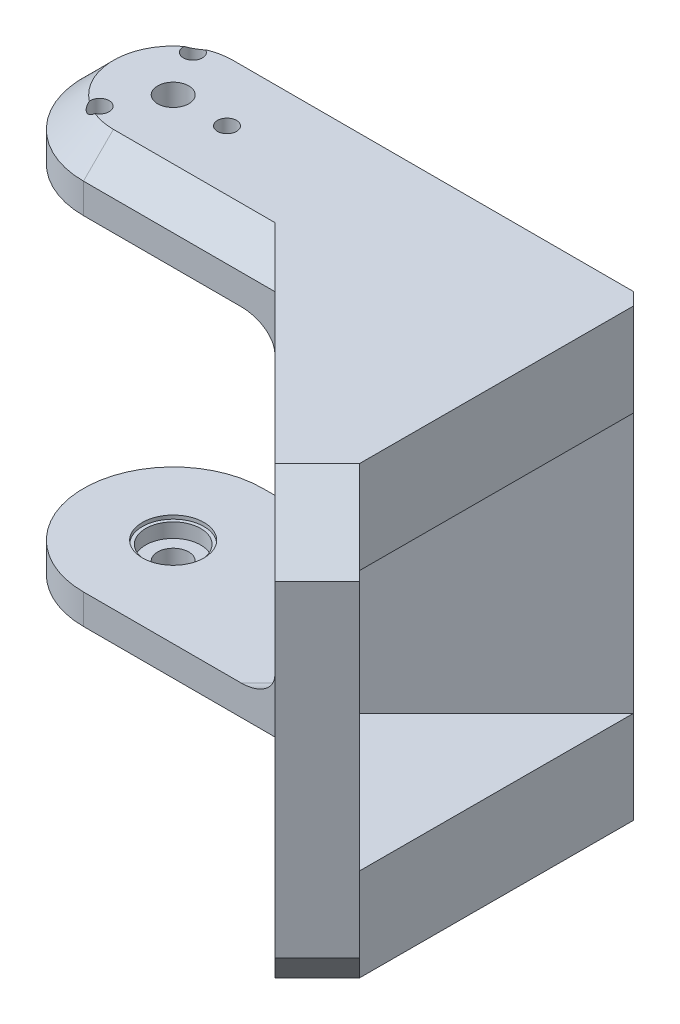
SolidWorks part; units mm, degrees
ref_plane "前视基准面" through (0, 0, 0) normal (0, 0, 1) x (1, 0, 0)
ref_plane "上视基准面" through (0, 0, 0) normal (0, 1, 0) x (1, 0, 0)
ref_plane "右视基准面" through (0, 0, 0) normal (1, 0, 0) x (0, 0, -1)
other "Configuration Table"
sketch "草图1" plane through (0, 0, 0) normal (0, 1, 0) x (1, 0, 0)
  line L0 (0, 0) -> (9, 0) construction
  line L1 (0, 15) -> (62, 15)
  line L3 (32, -15) -> (0, -15)
  line L4 (62, 15) -> (32, -15)
  arc A0 (0, 15) -> (0, -15) centre (0, 0) ccw
  circle A1 centre (9, 0) radius 1.6
  circle A2 centre (-4.5, -7.7942) radius 1.6
  circle A3 centre (-4.5, 7.7942) radius 1.6
  dimension "D1" = 30
  dimension "D2" = 32
  dimension "D3" = 3.2
  dimension "D5" = 9
  dimension "D6" = 45
  dimension "D4" = 3
extrude "凸台-拉伸1" add sketch "草图1" along normal blind 10
sketch "草图3" plane through (23.5, 0, 23.5) normal (0.7071, 0, 0.7071) x (0.7071, 0, -0.7071)
  line L0 (54.4472, 10) -> (54.4472, 0) construction
  line L1 (12.0208, 10) -> (54.4472, 10)
  line L2 (12.0208, 10) -> (12.0208, -64.5)
  line L3 (12.0208, -64.5) -> (54.4472, -64.5)
  line L4 (54.4472, 10) -> (54.4472, -64.5)
  dimension "D1" = 74.5
extrude "凸台-拉伸2" add sketch "草图3" along normal blind 10
sketch "草图6" plane through (0, 10, 0) normal (0, 1, 0) x (1, 0, 0)
  line L0 (39.0711, -22.0711) -> (68.9817, -51.9817)
  line L1 (68.9817, -51.9817) -> (76.0528, -44.9106)
  line L2 (76.0528, -44.9106) -> (46.1421, -15)
  line L3 (69.0711, 7.9289) -> (39.0711, -22.0711) construction
  line L4 (46.1421, -15) -> (39.0711, -22.0711)
  dimension "D1" = 10
  dimension "D2" = 42.3
extrude "凸台-拉伸3" add sketch "草图6" against normal up to surface (74.5 mm away) up to face at (50.5355, -64.5, 3.5355)
sketch "草图7" plane through (15.5711, 0, -15.5711) normal (0.7071, 0, -0.7071) x (-0.7071, 0, -0.7071)
  line L0 (-79.884, -11.75) -> (-48.884, -11.75) construction
  line L1 (-79.884, -11.75) -> (-79.884, -42.75) construction
  line L4 (-85.534, -64.5) -> (-85.534, 10) construction
  line L5 (-85.534, -27.25) -> (-43.234, -27.25) construction
  line L6 (-43.234, -64.5) -> (-43.234, 10) construction
  circle A0 centre (-79.884, -11.75) radius 1.6
  circle A1 centre (-48.884, -11.75) radius 1.6
  circle A2 centre (-48.884, -42.75) radius 1.6
  circle A3 centre (-79.884, -42.75) radius 1.6
  dimension "D6" = 3.2
  dimension "D7" = 15.5
  dimension "D8" = 5.65
  dimension "D3" = 90
  dimension "D4" = 31
  dimension "D5" = 31
  dimension "D1" = 2
  dimension "D2" = 2
extrude "切除-拉伸1" cut sketch "草图7" against normal up to surface (10 mm away) up to face at (46.7927, -21.8, 29.7927)
sketch "草图9" plane through (15.5711, 0, -15.5711) normal (0.7071, 0, -0.7071) x (-0.7071, 0, -0.7071)
  line L0 (-79.884, -11.75) -> (-48.884, -42.75) construction
  circle A0 centre (-64.384, -27.25) radius 18.6
  dimension "D1" = 37.2
extrude "切除-拉伸2" cut sketch "草图9" against normal blind 7
sketch "草图10" plane through (10.6213, 0, -10.6213) normal (0.7071, 0, -0.7071) x (-0.7071, 0, -0.7071)
  circle A0 centre (-64.384, -27.25) radius 13
  circle A1 centre (-64.384, -27.25) radius 18.6 construction
  dimension "D1" = 26
extrude "切除-拉伸3" cut sketch "草图10" against normal blind 7
chamfer "倒角1" distance 10 angle 45 2 edges at (72.5172, -64.5, 48.4462) (72.5172, 10, 48.4462)
sketch "草图11" plane through (0, 10, 0) normal (0, 1, 0) x (1, 0, 0)
  line L0 (69.0711, 7.9289) -> (68.9817, -37.8395)
  line L1 (68.9817, -37.8395) -> (46.1421, -15)
  line L2 (46.1421, -15) -> (69.0711, 7.9289)
extrude "凸台-拉伸4" add sketch "草图11" against normal blind 15.5
sketch "草图12" plane through (0, -64.5, 0) normal (0, -1, 0) x (1, 0, 0)
  line L3 (46.1421, 15) -> (69.0711, -7.9289)
  line L4 (69.0711, -7.9289) -> (68.9817, 37.8395)
  line L5 (68.9817, 37.8395) -> (46.1421, 15)
  line L6 (46.1421, 15) -> (69.0711, -7.9289)
  line L7 (69.0711, -7.9289) -> (68.9817, 37.8395)
  line L8 (68.9817, 37.8395) -> (46.1421, 15)
  dimension "D1" = 0
extrude "凸台-拉伸6" add sketch "草图12" against normal blind 15.5
sketch "草图13" plane through (0, 0, 0) normal (0, -1, 0) x (1, 0, 0)
  circle A0 centre (0, 0) radius 12.5
  circle A1 centre (9, 0) radius 1.6 construction
  circle A2 centre (-4.5, -7.7942) radius 1.6 construction
  circle A3 centre (-4.5, 7.7942) radius 1.6 construction
  circle A4 centre (9, 0) radius 1.6
  circle A5 centre (-4.5, -7.7942) radius 1.6
  circle A6 centre (-4.5, 7.7942) radius 1.6
  dimension "D1" = 25
extrude "凸台-拉伸7" add sketch "草图13" along normal blind 1
sketch "草图14" plane through (0, -64.5, 0) normal (0, -1, 0) x (1, 0, 0)
  line L3 (62, -15) -> (32, 15)
  line L4 (32, 15) -> (0, 15)
  line L5 (0, -15) -> (62, -15)
  line L6 (62, -15) -> (32, 15)
  line L7 (32, 15) -> (0, 15)
  line L8 (0, -15) -> (62, -15)
  arc A1 (0, 15) -> (0, -15) centre (0, 0) ccw
  arc A2 (0, 15) -> (0, -15) centre (0, 0) ccw
  dimension "D1" = 0
extrude "凸台-拉伸8" add sketch "草图14" against normal blind 10
sketch "草图15" plane through (0, -54.5, 0) normal (0, 1, 0) x (1, 0, 0)
  circle A0 centre (0, 0) radius 4.6
  dimension "D1" = 9.2
extrude "切除-拉伸4" cut sketch "草图15" against normal blind 3
sketch "草图16" plane through (0, -54.5, 0) normal (0, 1, 0) x (1, 0, 0)
  circle A0 centre (0, 0) radius 5.15
  dimension "D1" = 10.3
extrude "切除-拉伸5" cut sketch "草图16" against normal blind 0.6
sketch "草图17" plane through (0, -64.5, 0) normal (0, -1, 0) x (1, 0, 0)
  circle A0 centre (0, 0) radius 2.6
  dimension "D1" = 5.2
extrude "切除-拉伸6" cut sketch "草图17" against normal through all
chamfer "倒角2" distance 5 angle 45 6 edges at (31, 10, -15) (16, 10, 15) (-15, 10, 0) (16, -64.5, 15) (31, -64.5, -15) (-15, -64.5, 0)
fillet "圆角2" radius 4 2 edges at (47, -54.5, 0) (47, 0, 0)
